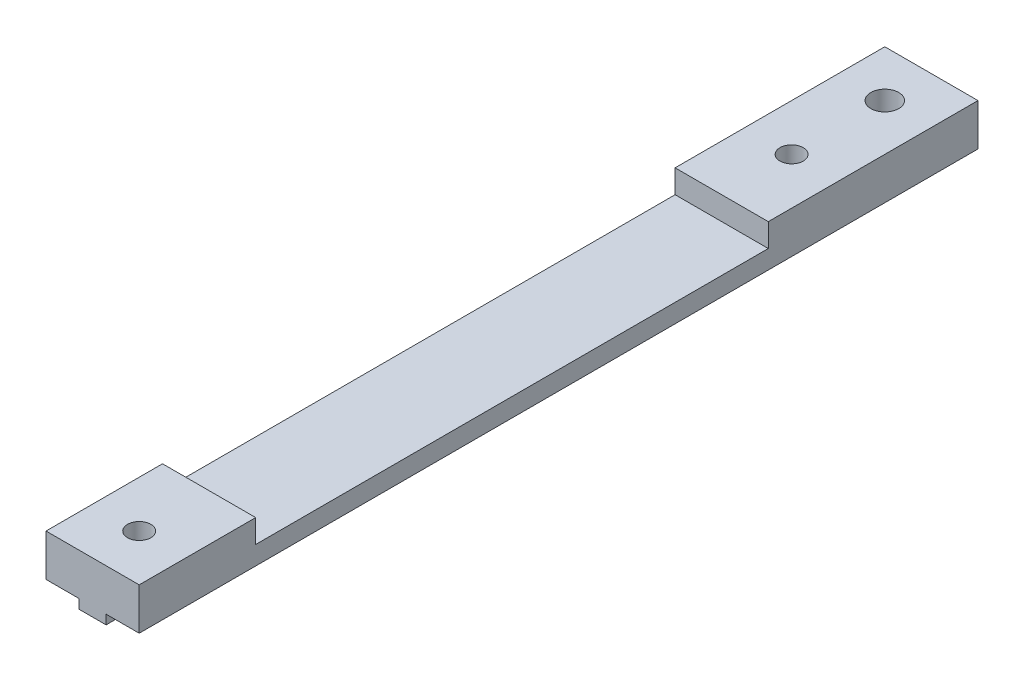
SolidWorks part; units mm, degrees
ref_plane "Front Plane" through (0, 0, 0) normal (0, 0, 1) x (1, 0, 0)
ref_plane "Top Plane" through (0, 0, 0) normal (0, 1, 0) x (1, 0, 0)
ref_plane "Right Plane" through (0, 0, 0) normal (1, 0, 0) x (0, 0, -1)
sketch "Sketch1" plane through (0, 0, 0) normal (0, 0, 1) x (1, 0, 0)
  line L0 (-5, 0) -> (5, 0)
  line L1 (5, 0) -> (5, -4.5)
  line L2 (5, -4.5) -> (1.45, -4.5)
  line L3 (1.45, -4.5) -> (1.45, -5.5)
  line L4 (1.45, -5.5) -> (-1.45, -5.5)
  line L5 (-1.45, -5.5) -> (-1.45, -4.5)
  line L6 (-1.45, -4.5) -> (-5, -4.5)
  line L7 (-5, -4.5) -> (-5, 0)
  point P9 (0, 0)
  dimension "D1" = 10
  dimension "D2" = 4.5
  dimension "D3" = 1
  dimension "D4" = 2.9
extrude "Main" add sketch "Sketch1" along normal blind 90
sketch "Sketch2" plane through (0, 0, 0) normal (0, 1, 0) x (1, 0, 0)
  line L0 (5, -90) -> (-5, -90) construction
  line L1 (5, 0) -> (-5, 0) construction
  circle A0 centre (0, -85) radius 1.25
  circle A1 centre (0, -15) radius 1.25
  circle A2 centre (0, -5) radius 1.5
  dimension "D1" = 2.5
  dimension "D4" = 3
  dimension "D2" = 5
  dimension "D3" = 70
  dimension "D5" = 5
extrude "MainHoles" cut sketch "Sketch2" against normal through all
sketch "Sketch3" plane through (0, 0, 0) normal (0, 1, 0) x (1, 0, 0)
  line L1 (-5, -90) -> (-5, 0) construction
  line L5 (5, -90) -> (5, 0) construction
  line L6 (-5, -22.5) -> (5, -22.5)
  line L7 (-5, -22.5) -> (-5, -77.5)
  line L8 (-5, -77.5) -> (5, -77.5)
  line L9 (5, -22.5) -> (5, -77.5)
  line L10 (5, -90) -> (-5, -90) construction
  point P0 (-5, -35)
  dimension "D2" = 55
  dimension "D3" = 12.5
extrude "PinHoles" cut sketch "Sketch3" against normal blind 2.5
